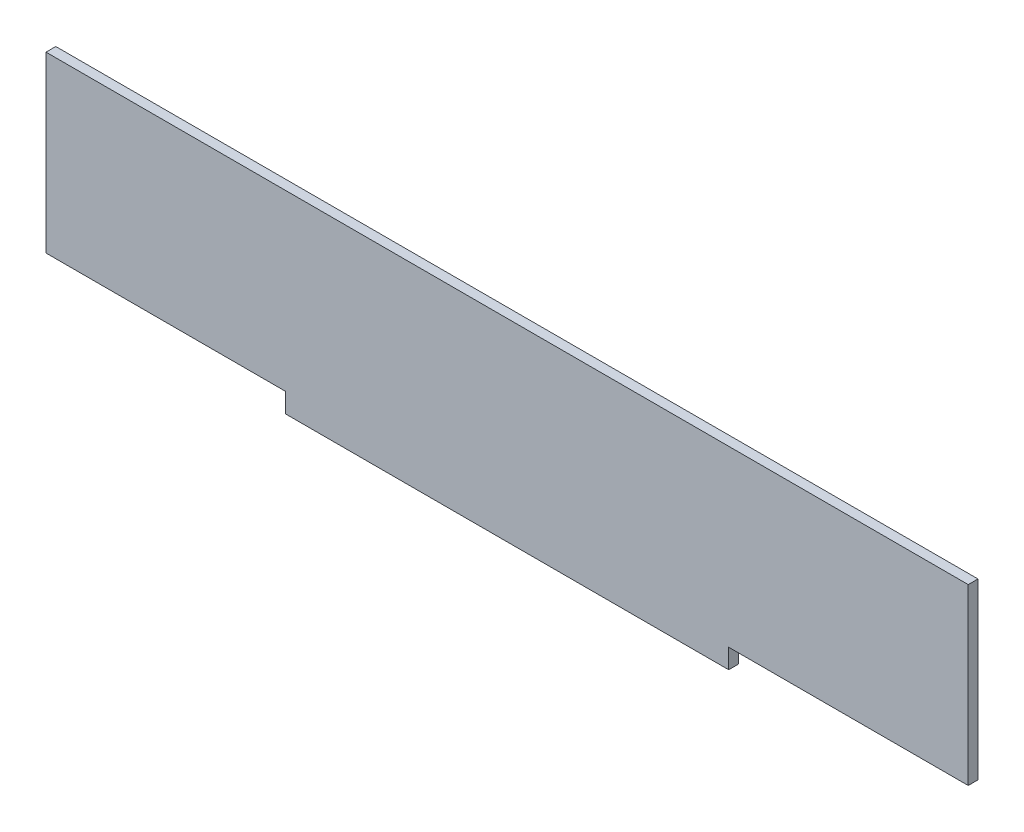
SolidWorks part; units mm, degrees
material "ABS"
ref_plane "X-Y Datum" through (0, 0, 0) normal (0, 0, 1) x (1, 0, 0)
ref_plane "X-Z Datum" through (0, 0, 0) normal (0, 1, 0) x (1, 0, 0)
ref_plane "Y-Z Datum" through (0, 0, 0) normal (1, 0, 0) x (0, 0, -1)
sketch "Sketch1" plane through (0, 0, 0) normal (0, 0, 1) x (1, 0, 0)
  line L1 (-149.85, 28.275) -> (149.85, 28.275)
  line L2 (-149.85, 28.275) -> (-149.85, -28.275)
  line L3 (-149.85, -28.275) -> (149.85, -28.275)
  line L4 (149.85, 28.275) -> (149.85, -28.275)
  line L5 (-149.85, 28.275) -> (149.85, -28.275) construction
  line L6 (-149.85, -28.275) -> (149.85, 28.275) construction
  point P0 (0, 0)
  dimension "D1" = 56.55
  dimension "D2" = 299.7
extrude "Boss-Extrude1" add sketch "Sketch1" along normal blind 3.175
sketch "Sketch2" plane through (0, -28.275, 0) normal (0, -1, 0) x (1, 0, 0)
  line L0 (0, 0) -> (0, 3.175) construction
  line L1 (-149.85, 3.175) -> (149.85, 3.175) construction
  line L2 (-149.85, 0) -> (149.85, 0) construction
  line L3 (-72, 3.175) -> (72, 3.175)
  line L4 (-72, 3.175) -> (-72, 0)
  line L5 (-72, 0) -> (72, 0)
  line L6 (72, 3.175) -> (72, 0)
  line L7 (-72, 3.175) -> (72, 0) construction
  line L8 (-72, 0) -> (72, 3.175) construction
  point P5 (0, 1.5875)
  point P10 (5.4756, 0)
  point P11 (-71, 0)
  dimension "D1" = 144
extrude "Boss-Extrude2" add sketch "Sketch2" along normal blind 6.35
